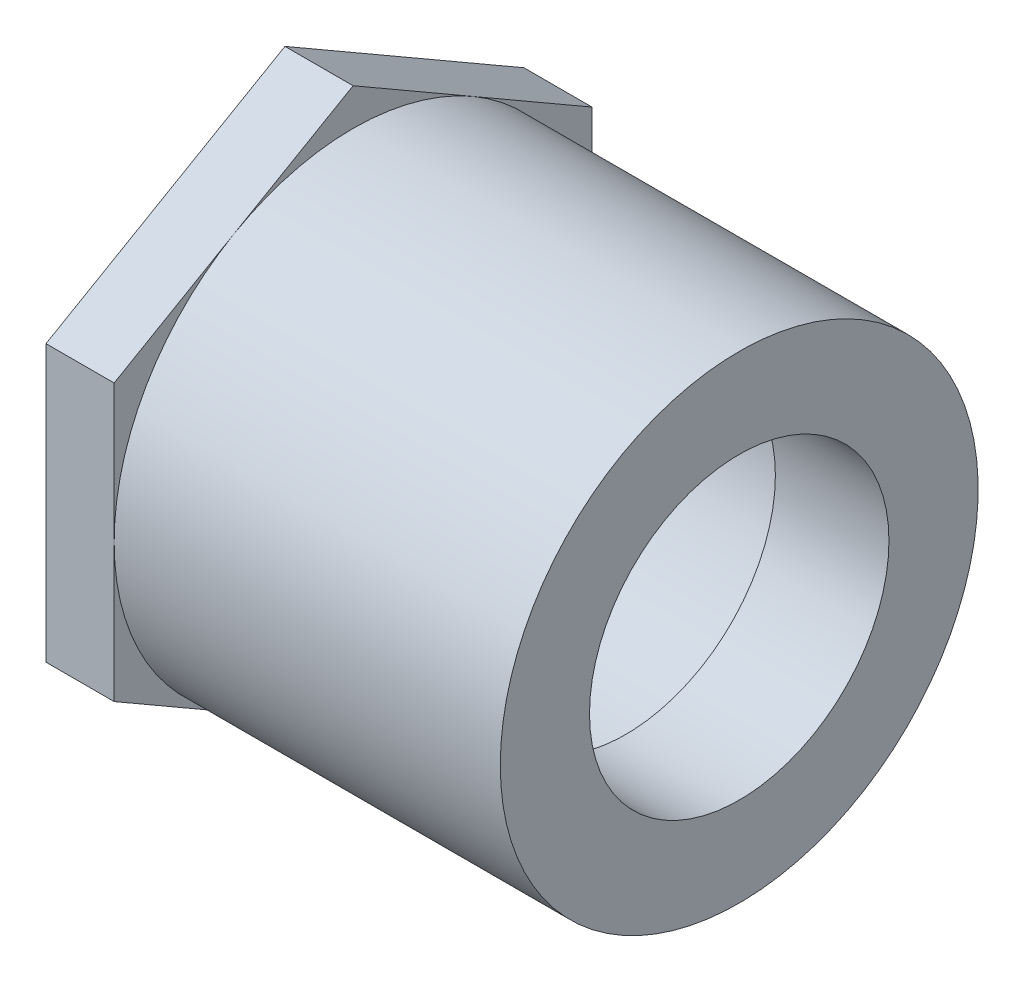
SolidWorks part; units mm, degrees
ref_plane "Front Plane" through (0, 0, 0) normal (0, 0, 1) x (1, 0, 0)
ref_plane "Top Plane" through (0, 0, 0) normal (0, 1, 0) x (1, 0, 0)
ref_plane "Right Plane" through (0, 0, 0) normal (1, 0, 0) x (0, 0, -1)
sketch "Sketch0" plane through (0, 0, 0) normal (0, 0, 1) x (1, 0, 0)
  line L0 (-31.75, 0) -> (0, 0) construction
  line L2 (-22.225, 16.7005) -> (-22.225, -16.7005) construction
  line L3 (-26.9875, 16.7005) -> (-26.9875, -16.7005) construction
  line L5 (-7.9375, 13.2842) -> (-31.75, 13.4366) construction
  line L6 (-7.9375, 13.2842) -> (-7.9375, -13.2842) construction
  line L7 (-7.9375, -13.2842) -> (-31.75, -13.4366) construction
  line L8 (-31.75, 13.4366) -> (-31.75, -13.4366) construction
  line L14 (-7.9375, 10.4648) -> (-7.9375, -10.4648) construction
  line L21 (-31.75, 0) -> (-7.9375, 0) construction
  point P12 (-22.225, 0)
  point P27 (-26.9875, 0)
  dimension "A" = 31.75
  dimension "OD A 2" = 26.8732
  dimension "OD B 2" = 26.5684
  dimension "ID 2" = 20.9296
  dimension "B" = 7.9375
  dimension "Pipe OD 1" = 33.401
  dimension "C 1" = 22.225
  dimension "J" = 33.401
  dimension "K" = 4.7625
sketch "Sketch1" plane through (0, 0, 0) normal (0, 0, 1) x (1, 0, 0)
  line L0 (-31.75, 0) -> (0, 0) construction
  line L1 (-31.75, 0) -> (0, 0) construction
  line L2 (-31.75, -16.7005) -> (0, -16.7005)
  line L3 (0, -10.4648) -> (0, -16.7005)
  line L4 (-31.75, -16.7005) -> (-31.75, -13.4366)
  line L5 (-31.75, -13.4366) -> (-7.9375, -13.2842)
  line L6 (0, 0) -> (0, -10.4648) construction
  line L8 (-7.9375, -10.4648) -> (-7.9375, -13.2842)
  line L11 (-7.9375, -10.4648) -> (0, -10.4648)
revolve "Revolve1" add sketch "Sketch1" angle 360 about L1
sketch "Sketch2" plane through (-31.75, 0, 0) normal (-1, 0, 0) x (0, 0, 1)
  line L0 (0, 0) -> (0, 19.2841) construction
  line L1 (0, 19.2841) -> (-16.7005, 9.642)
  line L2 (-16.7005, 9.642) -> (-16.7005, -9.642)
  line L3 (-16.7005, -9.642) -> (0, -19.2841)
  line L4 (0, -19.2841) -> (16.7005, -9.642)
  line L5 (16.7005, -9.642) -> (16.7005, 9.642)
  line L6 (16.7005, 9.642) -> (0, 19.2841)
  circle A0 centre (0, 0) radius 13.4366 construction
  circle A1 centre (0, 0) radius 13.4366
  circle A2 centre (0, 0) radius 16.7005 construction
  point P3 (0, 16.7005)
extrude "Boss-Extrude1" add sketch "Sketch2" against normal up to vertex (4.7625 mm away) up to point (-26.9875, 0, 0)
